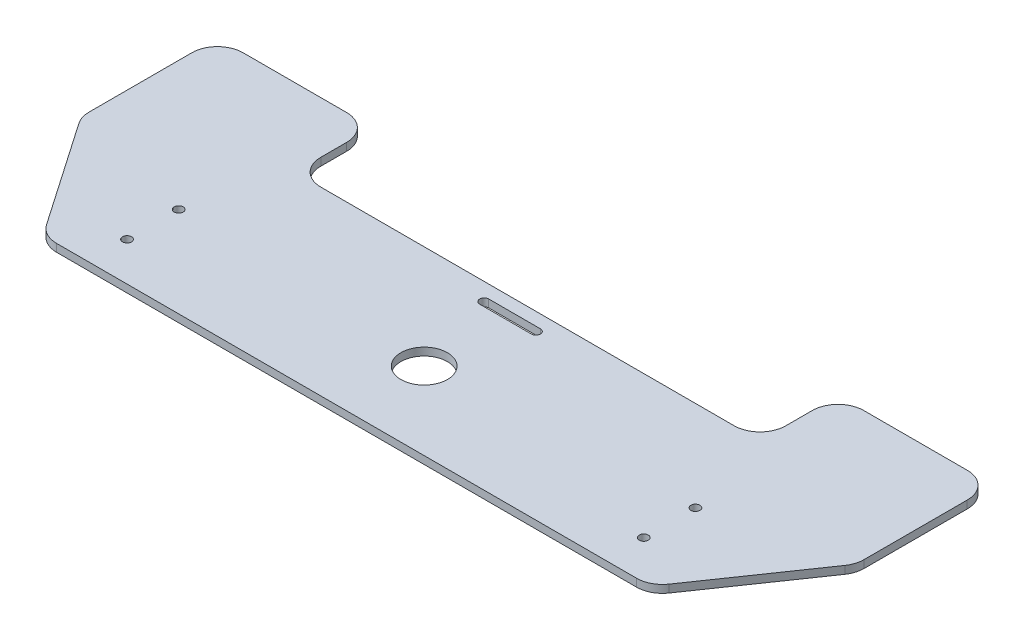
SolidWorks part; units mm, degrees
ref_plane "前视基准面" through (0, 0, 0) normal (0, 0, 1) x (1, 0, 0)
ref_plane "上视基准面" through (0, 0, 0) normal (0, 1, 0) x (1, 0, 0)
ref_plane "右视基准面" through (0, 0, 0) normal (1, 0, 0) x (0, 0, -1)
other "Configuration Table"
sketch "草图1" plane through (0, 0, 0) normal (0, 1, 0) x (1, 0, 0)
  line L5 (-148.2358, 19.5134) -> (-120.4921, -20.7712)
  line L6 (-150, 25.1854) -> (-150, 65)
  line L8 (0, 0) -> (0, 50000) construction
  line L13 (-140.0992, 74.9008) -> (-100, 74.9008)
  line L14 (0, 0.3213) -> (-0.1034, 0.2697) construction
  line L15 (-150, 74.9008) -> (-146.0376, 72.9222) construction
  line L16 (-90, 64.9008) -> (-90, 54.9008)
  line L17 (-80, 44.9008) -> (80, 44.9008)
  line L18 (-112.2563, -25.0992) -> (112.2563, -25.0992)
  line L19 (149.8966, 75.1705) -> (145.9342, 73.1919) construction
  line L20 (0, 0.2309) -> (-0.1034, 0.2697) construction
  line L21 (90, 64.9008) -> (90, 54.9008)
  line L22 (140.1011, 75.0927) -> (100.0019, 75.0927)
  line L23 (150, 25.1854) -> (150, 65)
  line L24 (148.2358, 19.5134) -> (120.4921, -20.7712)
  arc A10 (-90, 54.9008) -> (-80, 44.9008) centre (-80, 54.9008) ccw
  arc A11 (-90, 64.9008) -> (-100, 74.9008) centre (-100, 64.9008) ccw
  arc A12 (-150, 65) -> (-140.0992, 74.9008) centre (-140.0992, 65) cw
  arc A13 (-148.2358, 19.5134) -> (-150, 25.1854) centre (-140, 25.1854) cw
  arc A14 (-120.4921, -20.7712) -> (-112.2563, -25.0992) centre (-112.2563, -15.0992) ccw
  arc A15 (120.4921, -20.7712) -> (112.2563, -25.0992) centre (112.2563, -15.0992) cw
  arc A16 (148.2358, 19.5134) -> (150, 25.1854) centre (140, 25.1854) ccw
  arc A17 (150, 65) -> (140.1011, 75.0927) centre (140.1011, 65.1919) ccw
  arc A18 (90, 64.9008) -> (100.0019, 75.0927) centre (99.9982, 65.0927) cw
  arc A19 (90, 54.9008) -> (80, 44.9008) centre (80, 54.9008) cw
  point P0 (0, 0)
  point P17 (0, 25.2697)
  point P39 (0, 44.9008)
  point P40 (0, -25.0992)
  dimension "D1" = 60
extrude "凸台-拉伸1" add sketch "草图1" along normal blind 3
sketch "草图2" plane through (0, 3, 0) normal (0, 1, 0) x (1, 0, 0)
  line L1 (102.5393, 24.9008) -> (97.4607, 24.9008) construction
  line L2 (100, 24.9008) -> (100, -49975.0992) construction
  line L3 (-112.2563, -25.0992) -> (112.2563, -25.0992) construction
  line L4 (0, 0) -> (0, 50000) construction
  circle A0 centre (100, 9.9008) radius 1.75
  circle A1 centre (100, -10.0992) radius 1.75
  circle A2 centre (-100, -10.0992) radius 1.75
  circle A3 centre (-100, 9.9008) radius 1.75
  point P8 (100, 24.9008)
  dimension "D1" = 3.5
  dimension "D3" = 3.5
  dimension "D4" = 15
  dimension "D2" = 15
extrude "切除-拉伸1" cut sketch "草图2" against normal blind 10
sketch "草图3" plane through (0, 3, 0) normal (0, 1, 0) x (1, 0, 0)
  line L0 (-10, 38.1508) -> (10, 38.1508) construction
  line L1 (-10, 39.9008) -> (10, 39.9008)
  line L2 (-10, 36.4008) -> (10, 36.4008)
  line L3 (0, 0) -> (0, 50000) construction
  line L4 (80, 44.9008) -> (-80, 44.9008) construction
  arc A0 (-10, 39.9008) -> (-10, 36.4008) centre (-10, 38.1508) ccw
  arc A1 (10, 36.4008) -> (10, 39.9008) centre (10, 38.1508) ccw
  point P2 (0, 38.1508)
  dimension "D1" = 1.75
  dimension "D2" = 20
  dimension "D3" = 5
extrude "切除-拉伸2" cut sketch "草图3" against normal blind 3
sketch "草图4" plane through (0, 3, 0) normal (0, 1, 0) x (1, 0, 0)
  circle A0 centre (0, 4.9008) radius 9
  dimension "D1" = 18
extrude "切除-拉伸3" cut sketch "草图4" against normal blind 10
